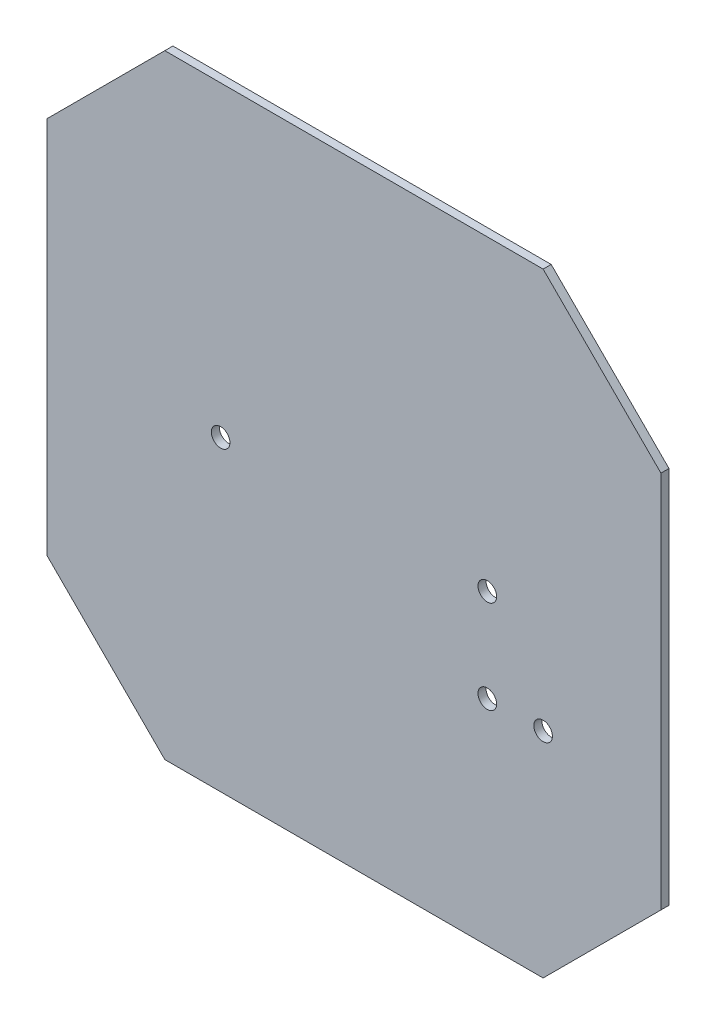
SolidWorks part; units mm, degrees
material "PVC Rigid"
ref_plane "Front Plane" through (0, 0, 0) normal (0, 0, 1) x (1, 0, 0)
ref_plane "Top Plane" through (0, 0, 0) normal (0, 1, 0) x (1, 0, 0)
ref_plane "Right Plane" through (0, 0, 0) normal (1, 0, 0) x (0, 0, -1)
sketch "Sketch1" plane through (0, 0, 0) normal (0, 0, 1) x (1, 0, 0)
  line L0 (-29.649, 62.0347) -> (-29.649, 1.0347)
  line L1 (-10.649, 81.0347) -> (-29.649, 62.0347)
  line L2 (-29.649, 1.0347) -> (-10.649, -17.9653)
  line L3 (50.351, -17.9653) -> (69.351, 1.0347)
  line L4 (69.351, 62.0347) -> (50.351, 81.0347)
  line L5 (-10.649, -17.9653) -> (50.351, -17.9653)
  line L6 (69.351, 1.0347) -> (69.351, 62.0347)
  line L7 (50.351, 81.0347) -> (-10.649, 81.0347)
  circle A0 centre (-1.649, 31.5347) radius 1.5
  circle A1 centre (41.351, 31.5347) radius 1.5
  circle A2 centre (41.351, 16.5347) radius 1.5
  circle A3 centre (50.351, 16.5347) radius 1.5
extrude "Boss-Extrude1" add sketch "Sketch1" along normal blind 1.3
